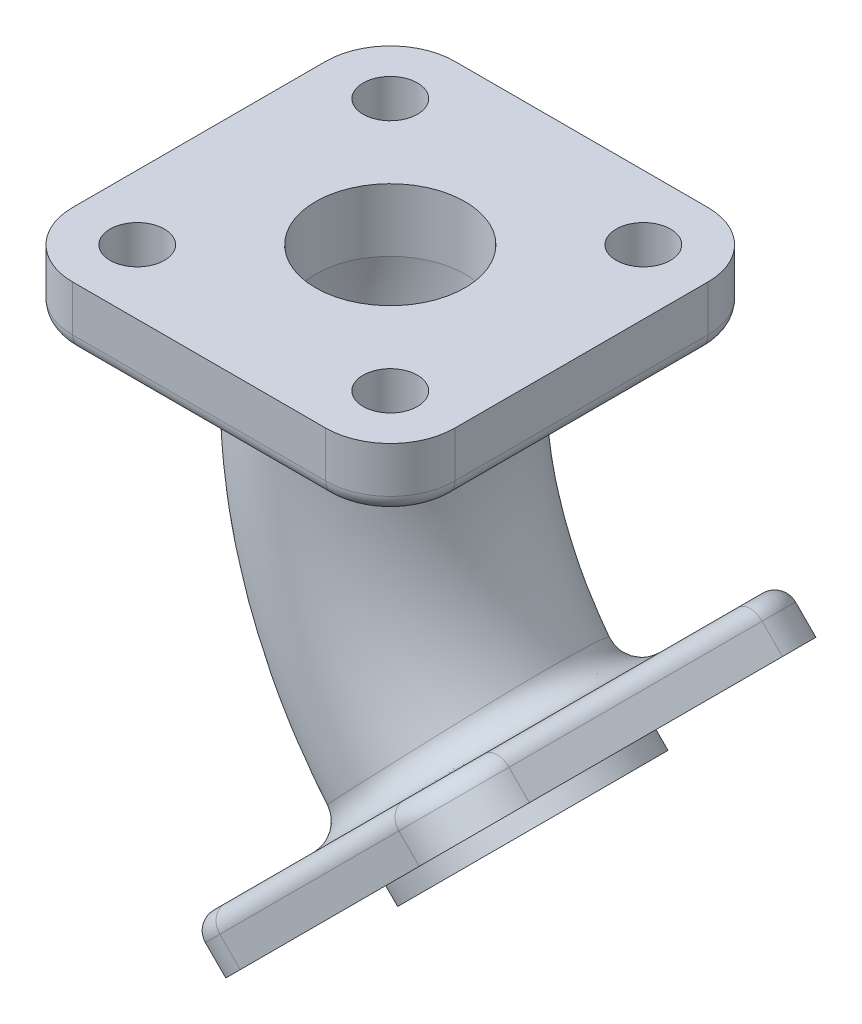
SolidWorks part; units mm, degrees
ref_plane "Alzado" through (0, 0, 0) normal (0, 0, 1) x (1, 0, 0)
ref_plane "Planta" through (0, 0, 0) normal (0, 1, 0) x (1, 0, 0)
ref_plane "Vista lateral" through (0, 0, 0) normal (1, 0, 0) x (0, 0, -1)
sketch "Croquis1" plane through (0, 0, 0) normal (0, 1, 0) x (1, 0, 0)
  line L1 (-74.5, -112.5) -> (74.5, -112.5)
  line L2 (-112.5, -74.5) -> (-112.5, 74.5)
  line L3 (-74.5, 112.5) -> (74.5, 112.5)
  line L4 (112.5, -74.5) -> (112.5, 74.5)
  line L5 (-112.5, -112.5) -> (112.5, 112.5) construction
  line L6 (-112.5, 112.5) -> (112.5, -112.5) construction
  arc A0 (-74.5, -112.5) -> (-112.5, -74.5) centre (-74.5, -74.5) cw
  arc A1 (74.5, -112.5) -> (112.5, -74.5) centre (74.5, -74.5) ccw
  arc A2 (74.5, 112.5) -> (112.5, 74.5) centre (74.5, 74.5) cw
  arc A3 (-112.5, 74.5) -> (-74.5, 112.5) centre (-74.5, 74.5) cw
  circle A4 centre (0, 0) radius 44
  circle A5 centre (-74.5, 74.5) radius 16
  circle A6 centre (74.5, -74.5) radius 16
  circle A7 centre (-74.5, -74.5) radius 16
  circle A8 centre (74.5, 74.5) radius 16
  point P0 (0, 0)
  dimension "D3" = 38
  dimension "D4" = 88
  dimension "D5" = 32
  dimension "D6" = 32
  dimension "D1" = 225
  dimension "D2" = 225
extrude "Saliente-Extruir1" add sketch "Croquis1" along normal blind 37
sketch "Croquis2" plane through (0, 0, 0) normal (0, 0, 1) x (1, 0, 0)
  line L0 (-74.5, 0) -> (74.5, 0) construction
  line L1 (38.5562, -253.3645) -> (159.7458, -132.1749) construction
  arc A0 (0, 0) -> (77.3374, -214.5833) centre (221.1341, -41.5298) ccw
  dimension "D1" = 225
  dimension "D2" = 45
sketch "Croquis3" plane through (0, 0, 0) normal (0, 1, 0) x (1, 0, 0)
  circle A0 centre (0, 0) radius 68.5
  circle A1 centre (0, 0) radius 44
  dimension "D1" = 137
  dimension "D2" = 88
sweep "Barrer1" add profiles "Croquis3" path "Croquis2"
sketch "Croquis4" plane through (0, 0, 0) normal (0, 0, 1) x (1, 0, 0)
  line L0 (-34.6569, -284.9469) -> (120.7102, -129.5798)
  line L1 (-74.5, 0) -> (74.5, 0) construction
  line L3 (-34.6569, -284.9469) -> (120.7102, -284.9469)
  line L4 (120.7102, -284.9469) -> (120.7102, -129.5798)
  dimension "D1" = 45
extrude "Cortar-Extruir1" cut sketch "Croquis4" against normal blind 84 and the other way blind 84
sketch "Croquis5" plane through (125.145, -125.145, 0) normal (0.7071, -0.7071, 0) x (0, 0, -1)
  line L0 (31.1129, -64.1561) -> (112.5002, 17.2312) construction
  line L1 (-74.4998, -207.7688) -> (74.5002, -207.7688)
  line L2 (-112.4998, -169.7688) -> (-112.4998, -20.7688)
  line L3 (-74.4998, 17.2312) -> (74.5002, 17.2312)
  line L4 (112.5002, -169.7688) -> (112.5002, -20.7688)
  line L5 (-112.4998, -207.7688) -> (-31.1125, -126.3815) construction
  line L6 (-112.4998, 17.2312) -> (-31.1125, -64.1561) construction
  line L7 (31.1129, -126.3815) -> (112.5002, -207.7688) construction
  circle A0 centre (0.0002, -95.2688) radius 44
  arc A1 (-74.4998, -207.7688) -> (-112.4998, -169.7688) centre (-74.4998, -169.7688) cw
  arc A2 (74.5002, -207.7688) -> (112.5002, -169.7688) centre (74.5002, -169.7688) ccw
  arc A3 (74.5002, 17.2312) -> (112.5002, -20.7688) centre (74.5002, -20.7688) cw
  arc A4 (-112.4998, -20.7688) -> (-74.4998, 17.2312) centre (-74.4998, -20.7688) cw
  circle A5 centre (-74.4998, -20.7688) radius 16
  circle A6 centre (74.5002, -169.7688) radius 16
  circle A7 centre (74.5002, -20.7688) radius 16
  circle A8 centre (-74.4998, -169.7688) radius 16
  point P0 (0.0002, -95.2688)
  dimension "D3" = 38
  dimension "D4" = 32
  dimension "D5" = 32
  dimension "D1" = 225
  dimension "D2" = 225
extrude "Saliente-Extruir2" add sketch "Croquis5" along normal blind 27
sketch "Croquis6" plane through (144.2369, -144.2369, 0) normal (0.7071, -0.7071, 0) x (0, 0, -1)
  circle A0 centre (0.0002, -95.2688) radius 44
  circle A1 centre (0.0002, -95.2688) radius 44 construction
  circle A2 centre (0.0002, -95.2688) radius 65
  dimension "D1" = 88
  dimension "D2" = 130
extrude "Saliente-Extruir3" add sketch "Croquis6" along normal blind 10
fillet "Redondeo1" radius 15 2 edges at (58.9426, -191.3474, -68.3663) (0, 0, 68.5)
fillet "Redondeo2" radius 10 16 edges at (-13.8997, -264.1897, 101.3698) (57.7798, -192.5102, 112.4998) (129.4592, -120.8308, 101.3698) (137.3293, -112.9607, -0.0002) (129.4592, -120.8308, -101.3703) (57.7798, -192.5102, -112.5002) (-13.8997, -264.1897, -101.3703) (101.3701, 0, 101.3701) (0, 0, 112.5) (-101.3701, 0, 101.3701) (-112.5, 0, 0) (-101.3701, 0, -101.3701) (0, 0, -112.5) (101.3701, 0, -101.3701) (-21.7697, -272.0598, -0.0002) (112.5, 0, 0)
